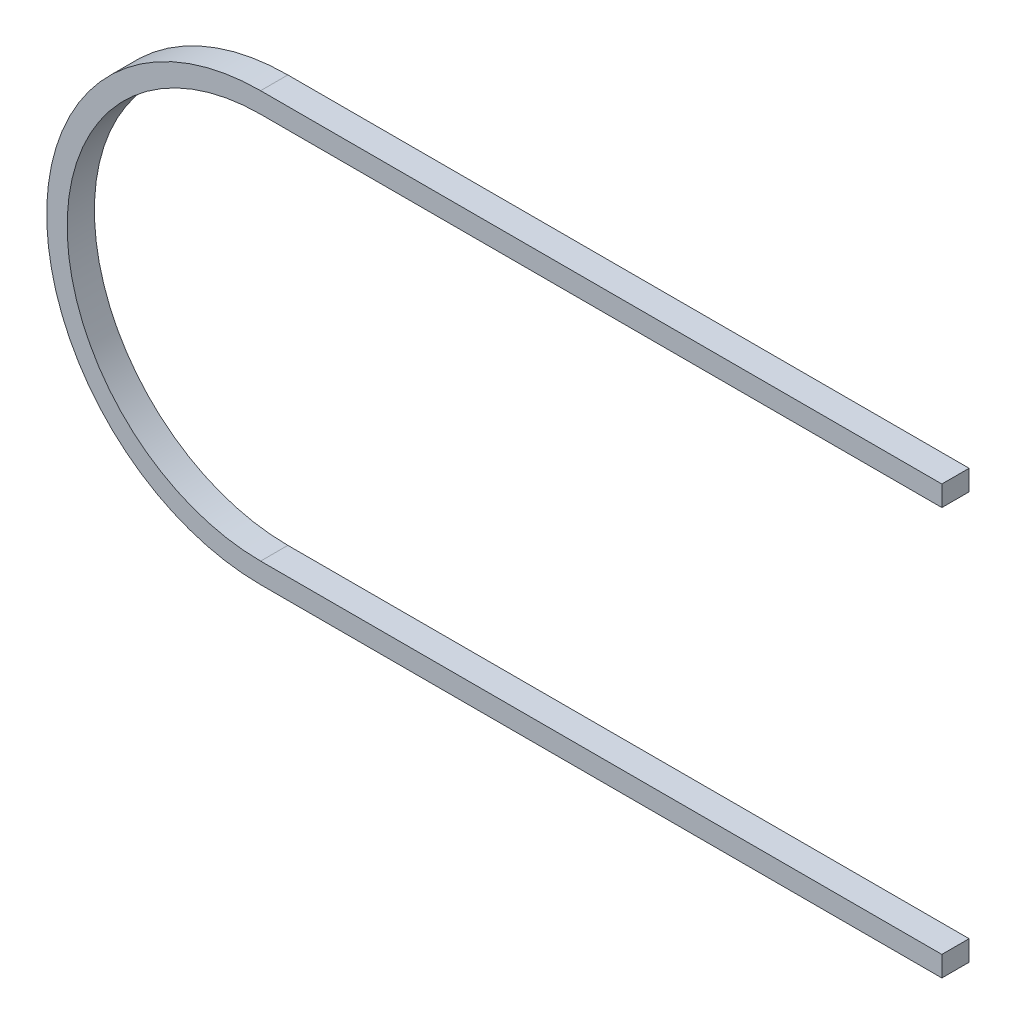
SolidWorks part; units mm, degrees
ref_plane "Front Plane" through (0, 0, 0) normal (0, 0, 1) x (1, 0, 0)
ref_plane "Top Plane" through (0, 0, 0) normal (0, 1, 0) x (1, 0, 0)
ref_plane "Right Plane" through (0, 0, 0) normal (1, 0, 0) x (0, 0, -1)
sketch "Sketch1" plane through (0, 0, 0) normal (0, 0, 1) x (1, 0, 0)
  line L0 (0, 19.939) -> (63.5, 19.939)
  line L1 (0, 18.034) -> (63.5, 18.034)
  line L2 (63.5, 18.034) -> (63.5, 19.939)
  line L3 (0, -18.034) -> (63.5, -18.034)
  line L4 (63.5, -18.034) -> (63.5, -19.939)
  line L5 (63.5, -19.939) -> (0, -19.939)
  arc A0 (0, 19.939) -> (0, -19.939) centre (0, 0) ccw
  arc A1 (0, 18.034) -> (0, -18.034) centre (0, 0) ccw
  dimension "D1" = 63.5
  dimension "D2" = 1.905
  dimension "D3" = 36.068
extrude "Boss-Extrude1" add sketch "Sketch1" along normal blind 2.54
